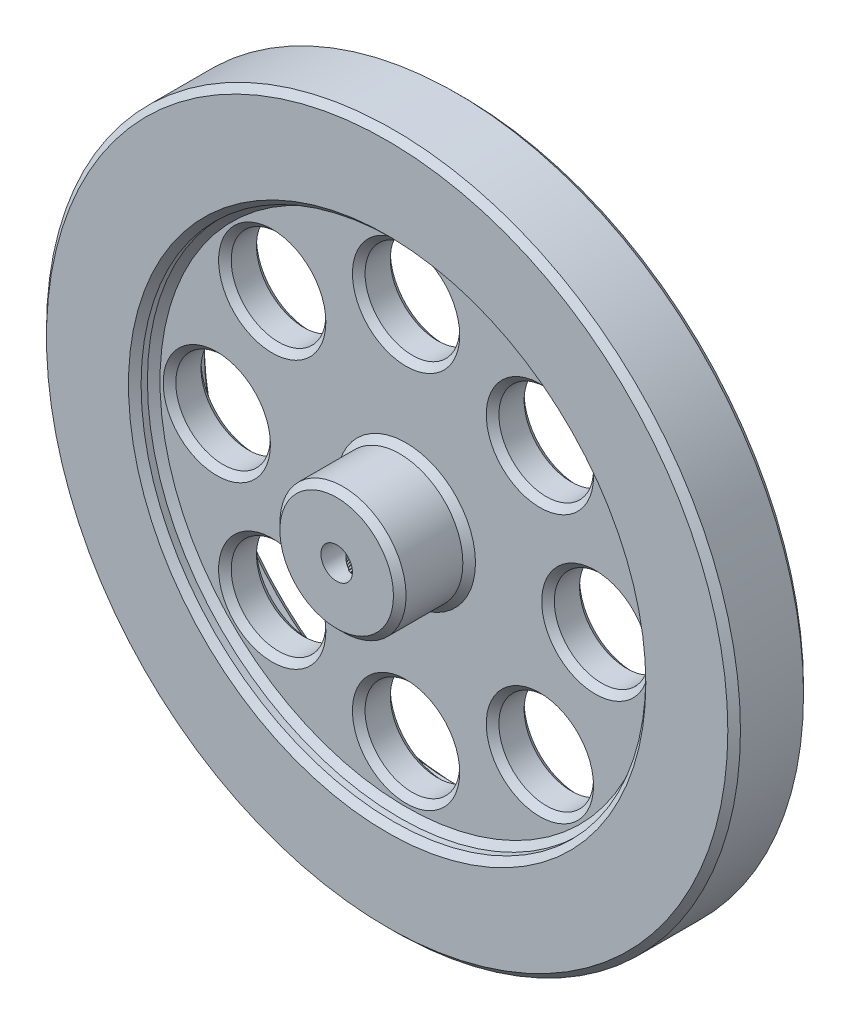
SolidWorks part; units mm, degrees
ref_plane "Front Plane" through (0, 0, 0) normal (0, 0, 1) x (1, 0, 0)
ref_plane "Top Plane" through (0, 0, 0) normal (0, 1, 0) x (1, 0, 0)
ref_plane "Right Plane" through (0, 0, 0) normal (1, 0, 0) x (0, 0, -1)
sketch "Sketch1" plane through (0, 0, 0) normal (0, 0, 1) x (1, 0, 0)
  circle A0 centre (0, 0) radius 55
  circle A1 centre (0, 0) radius 40
  circle A2 centre (0, 0) radius 30 construction
  circle A3 centre (0, 0) radius 10
  circle A4 centre (0, 30) radius 7.5
  circle A5 centre (21.2132, 21.2132) radius 7.5
  circle A6 centre (30, 0) radius 7.5
  circle A7 centre (21.2132, -21.2132) radius 7.5
  circle A8 centre (0, -30) radius 7.5
  circle A9 centre (-21.2132, -21.2132) radius 7.5
  circle A10 centre (-30, 0) radius 7.5
  circle A11 centre (-21.2132, 21.2132) radius 7.5
  point P24 (0, 0)
  dimension "D1" = 110
  dimension "D2" = 80
  dimension "D3" = 60
  dimension "D4" = 20
  dimension "D5" = 15
  dimension "D6" = 8
extrude "Boss-Extrude1" add sketch "Sketch1" along normal mid plane 12 contours A0 A1 region at (-53.4444, 0, 0)
extrude "Boss-Extrude2" add sketch "Sketch1<3>" along normal mid plane 6 contours A1 A11 A10 A9 A8 A7 A6 A5 A4 A3 region at (-38.8686, 0, 0)
sketch "Sketch1<3>" plane through (0, 0, 0) normal (0, 0, 1) x (1, 0, 0) same geometry as "Sketch1"
extrude "Boss-Extrude3" add sketch "Sketch1<4>" along normal blind 14 and the other way up to surface (3 mm away) contours A3 region at (0, 0, 0) other way up to face at (-13.7132, 21.2132, -3)
sketch "Sketch1<4>" plane through (0, 0, 0) normal (0, 0, 1) x (1, 0, 0) same geometry as "Sketch1"
chamfer "Chamfer1" distance 1 angle 45 1 edges at (10, 0, 14)
sketch "Sketch2" plane through (0, 0, 14) normal (0, 0, 1) x (1, 0, 0)
  circle A0 centre (0, 0) radius 2.5
  dimension "D1" = 5
extrude "Cut-Extrude1" cut sketch "Sketch2" against normal blind 35
sketch "Sketch3" plane through (0, 0, 0) normal (0, 1, 0) x (1, 0, 0)
  line L0 (-10, -3) -> (-10, -13) construction
  line L1 (40, 6) -> (-40, 6) construction
  circle A0 centre (0, -9) radius 2.5
  dimension "D1" = 5
  dimension "D2" = 10
  dimension "D3" = 15
extrude "Cut-Extrude2" cut sketch "Sketch3" against normal blind 35
ref_plane "Plane1" through (0, -10, 0) normal (0, -1, 0) x (-1, 0, 0)
thread "Thread1" pitch 0.5 method cut profile "Thread Profile1" start angle 0, offset 0.4, length 0, pitch 0.5, diameter 5
ref_plane "Plane2" through (2.5, -9.6, 9) normal (0, 0, 1) x (1, 0, 0)
sketch "Thread Profile1" plane through (2.5, -9.6, 9) normal (0, 0, 1) x (1, 0, 0)
  line L0 (0, 0) -> (0, 0.5) construction
  line L1 (0, 0) -> (0.2706, 0.1562)
  line L2 (0.2706, 0.1562) -> (0.2706, 0.2187)
  line L3 (0.2706, 0.2187) -> (0, 0.375)
  line L4 (0.2706, 0.1875) -> (0, 0.1875) construction
  line L11 (0, 0) -> (0, 0.375)
  point P2 (0, 0)
  dimension "Pitch" = 0.5
  dimension "Profile_Angle" = 60
  dimension "Profile_Land" = 0.0625
  dimension "Profile_Height" = 0.2706
chamfer "Chamfer2" distance 1 angle 45 4 edges at (40, 0, 6) (55, 0, -6) (55, 0, 6) (40, 0, -6)
chamfer "Chamfer3" distance 1 angle 45 20 edges at (40, 0, -3) (7.5, 30, -3) (28.7132, 21.2132, -3) (37.5, 0, -3) (28.7132, -21.2132, -3) (7.5, -30, -3) (-13.7132, -21.2132, -3) (-22.5, 0, -3) (-13.7132, 21.2132, -3) (2.5, 0, -3) (40, 0, 3) (10, 0, 3) (7.5, 30, 3) (28.7132, 21.2132, 3) (37.5, 0, 3) (28.7132, -21.2132, 3) (7.5, -30, 3) (-13.7132, -21.2132, 3) (-22.5, 0, 3) (-13.7132, 21.2132, 3)
